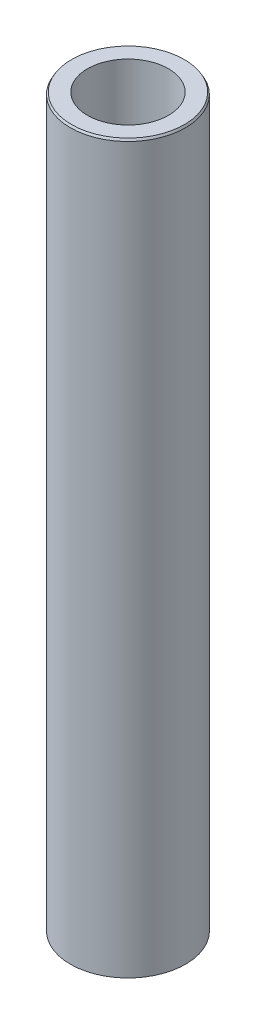
SolidWorks part; units mm, degrees
ref_plane "Front Plane" through (0, 0, 0) normal (0, 0, 1) x (1, 0, 0)
ref_plane "Top Plane" through (0, 0, 0) normal (0, 1, 0) x (1, 0, 0)
ref_plane "Right Plane" through (0, 0, 0) normal (1, 0, 0) x (0, 0, -1)
sketch "Sketch1" plane through (0, 0, 0) normal (0, 1, 0) x (1, 0, 0)
  circle A0 centre (0, 0) radius 47.5
  dimension "SHAFT_OD" = 95
extrude "Boss-Extrude1" add sketch "Sketch1" along normal blind 600
sketch "Sketch2" plane through (0, 0, 0) normal (0, 1, 0) x (1, 0, 0)
  circle A0 centre (0, 0) radius 33.3616
  dimension "BORE_D" = 66.7233
extrude "Cut-Extrude1" cut sketch "Sketch2" along normal through all
chamfer "Chamfer1" distance 1.7385 angle 30 2 edges at (0, 600, 47.5) (0, 0, 47.5) first distance on face at (0, 600, 47.5) first distance on face at (0, 0, 33.3616)
